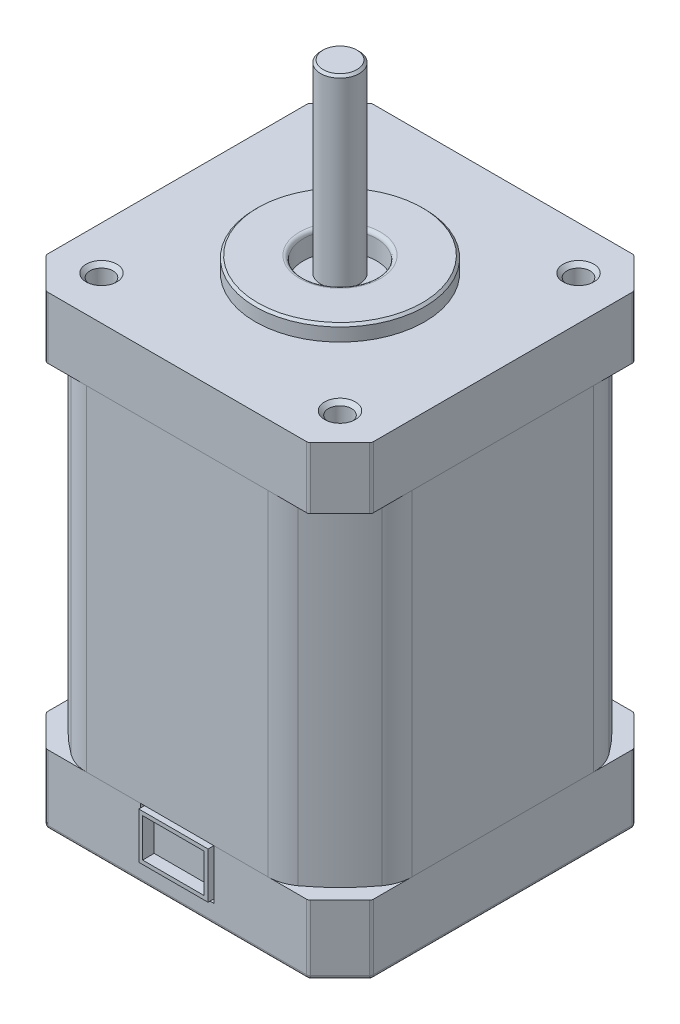
SolidWorks part; units mm, degrees
ref_plane "Спереди" through (0, 0, 0) normal (0, 0, 1) x (1, 0, 0)
ref_plane "Сверху" through (0, 0, 0) normal (0, 1, 0) x (1, 0, 0)
ref_plane "Справа" through (0, 0, 0) normal (1, 0, 0) x (0, 0, -1)
sketch "Эскиз1" plane through (0, 0, 0) normal (0, 1, 0) x (1, 0, 0)
  line L0 (-21.15, 17.0338) -> (-17.0338, 21.15)
  line L1 (-21.15, 21.15) -> (21.15, 21.15)
  line L2 (-21.15, 21.15) -> (-21.15, -21.15)
  line L3 (-21.15, -21.15) -> (21.15, -21.15)
  line L4 (21.15, 21.15) -> (21.15, -21.15)
  line L5 (-21.15, 21.15) -> (21.15, -21.15) construction
  line L6 (-21.15, -21.15) -> (21.15, 21.15) construction
  line L7 (-17.0338, 21.15) -> (17.0338, 21.15)
  line L8 (17.0338, 21.15) -> (21.15, 17.0338)
  line L9 (21.15, 17.0338) -> (21.15, -17.0338)
  line L10 (21.15, -17.0338) -> (17.0338, -21.15)
  line L11 (17.0338, -21.15) -> (-17.0338, -21.15)
  line L12 (-17.0338, -21.15) -> (-21.15, -17.0338)
  point P0 (0, 0)
  dimension "D1" = 42.3
  dimension "D2" = 54
extrude "Бобышка-Вытянуть1" add sketch "Эскиз1" along normal blind 9 contours L12 L3 L10 L4 L8 L1 L0 L2 region at (0, 0, 0)
extrude "Бобышка-Вытянуть2" add sketch "Эскиз1<3>" against normal blind 8 from offset 60.5 separate body contours L12 L3 L10 L4 L8 L1 L0 L2 region at (0, 0, 0)
sketch "Эскиз1<3>" plane through (0, 0, 0) normal (0, 1, 0) x (1, 0, 0) same geometry as "Эскиз1"
sketch "Эскиз2" plane through (0, 9, 0) normal (0, 1, 0) x (1, 0, 0)
  line L16 (-21.15, -17.0338) -> (-17.0338, -21.15)
  line L17 (-17.0338, -21.15) -> (17.0338, -21.15)
  line L18 (17.0338, -21.15) -> (21.15, -17.0338)
  line L19 (21.15, -17.0338) -> (21.15, 17.0338)
  line L20 (21.15, 17.0338) -> (17.0338, 21.15)
  line L21 (17.0338, 21.15) -> (-17.0338, 21.15)
  line L22 (-17.0338, 21.15) -> (-21.15, 17.0338)
  line L23 (-21.15, 17.0338) -> (-21.15, -17.0338)
  line L25 (-11.7974, -21.15) -> (11.7974, -21.15)
  line L27 (21.15, -11.7974) -> (21.15, 11.7974)
  line L29 (11.7974, 21.15) -> (-11.7974, 21.15)
  line L31 (-21.15, 11.7974) -> (-21.15, -11.7974)
  arc A0 (-20.1875, -14.7467) -> (-14.7467, -20.1875) centre (0, 0) ccw
  arc A1 (-14.7467, 20.1875) -> (-20.1875, 14.7467) centre (0, 0) ccw
  arc A2 (20.1875, 14.7467) -> (14.7467, 20.1875) centre (0, 0) ccw
  arc A3 (14.7467, -20.1875) -> (20.1875, -14.7467) centre (0, 0) ccw
  arc A4 (14.7467, 20.1875) -> (11.7974, 21.15) centre (11.7974, 16.15) ccw
  arc A5 (21.15, 11.7974) -> (20.1875, 14.7467) centre (16.15, 11.7974) ccw
  arc A6 (20.1875, -14.7467) -> (21.15, -11.7974) centre (16.15, -11.7974) ccw
  arc A7 (11.7974, -21.15) -> (14.7467, -20.1875) centre (11.7974, -16.15) ccw
  arc A8 (-14.7467, -20.1875) -> (-11.7974, -21.15) centre (-11.7974, -16.15) ccw
  arc A9 (-20.1875, -14.7467) -> (-21.15, -11.7974) centre (-16.15, -11.7974) cw
  arc A10 (-20.1875, 14.7467) -> (-21.15, 11.7974) centre (-16.15, 11.7974) ccw
  arc A11 (-11.7974, 21.15) -> (-14.7467, 20.1875) centre (-11.7974, 16.15) ccw
  point P22 (21.15, 13.3296)
  point P27 (13.3296, -21.15)
  point P36 (-13.3296, 21.15)
  dimension "D1" = 50
  dimension "D3" = 5
  dimension "D2" = 0
extrude "Бобышка-Вытянуть3" add sketch "Эскиз2" along normal blind 43.5 separate body
sketch "Эскиз3" plane through (0, 0, 0) normal (0, -1, 0) x (1, 0, 0)
  circle A0 centre (0, 0) radius 4.75
  dimension "D1" = 9.5
extrude "Вырез-Вытянуть1" cut sketch "Эскиз3" against normal blind 3
sketch "Эскиз4" plane through (0, 3, 0) normal (0, -1, 0) x (1, 0, 0)
  circle A0 centre (0, 0) radius 2.5
  circle A1 centre (0, 0) radius 4.75
  dimension "D1" = 5
extrude "Вырез-Вытянуть2" cut sketch "Эскиз4" against normal blind 0.5
sketch "Эскиз5" plane through (0, 3, 0) normal (0, -1, 0) x (1, 0, 0)
  circle A0 centre (0, 0) radius 0.5
  dimension "D1" = 1
extrude "Вырез-Вытянуть3" cut sketch "Эскиз5" against normal blind 0.5
chamfer "Фаска1" distance 0.3 angle 45 1 edges at (0, 3, -2.5)
fillet "Скругление1" radius 0.5 17 edges at (0, 0, 21.15) (19.0919, 0, 19.0919) (21.15, 0, 0) (19.0919, 0, -19.0919) (0, 0, -21.15) (-19.0919, 0, -19.0919) (-21.15, 0, 0) (-19.0919, 0, 19.0919) (0, 0, -4.75) (21.15, 4.5, 17.0338) (17.0338, 4.5, 21.15) (-17.0338, 4.5, 21.15) (-21.15, 4.5, 17.0338) (-21.15, 4.5, -17.0338) (-17.0338, 4.5, -21.15) (17.0338, 4.5, -21.15) (21.15, 4.5, -17.0338)
fillet "Скругление2" radius 0.5 8 edges at (21.15, 56.5, 17.0338) (17.0338, 56.5, 21.15) (-17.0338, 56.5, 21.15) (-21.15, 56.5, 17.0338) (-21.15, 56.5, -17.0338) (-17.0338, 56.5, -21.15) (17.0338, 56.5, -21.15) (21.15, 56.5, -17.0338)
sketch "Эскиз6" plane through (0, 60.5, 0) normal (0, 1, 0) x (1, 0, 0)
  circle A0 centre (0, 0) radius 11
  circle A1 centre (0, 0) radius 4.75
  dimension "D1" = 22
  dimension "D2" = 9.5
extrude "Бобышка-Вытянуть4" add sketch "Эскиз6" along normal blind 2
sketch "Эскиз7" plane through (0, 60.5, 0) normal (0, 1, 0) x (1, 0, 0)
  circle A2 centre (0, 0) radius 4.75
  circle A3 centre (0, 0) radius 4.75
  dimension "D1" = 0
extrude "Вырез-Вытянуть4" cut sketch "Эскиз7" against normal blind 1
chamfer "Фаска2" distance 0.3 angle 45 1 edges at (0, 62.5, 11)
fillet "Скругление3" radius 0.5 1 edges at (0, 62.5, 4.75)
sketch "Эскиз8" plane through (0, 60.5, 0) normal (0, 1, 0) x (1, 0, 0)
  circle A0 centre (0, 0) radius 2.5
  dimension "D1" = 5
extrude "Бобышка-Вытянуть5" add sketch "Эскиз8" along normal blind 24
chamfer "Фаска4" distance 0.3 angle 45 1 edges at (0, 84.5, 2.5)
sketch "Эскиз10" plane through (0, 0, 21.15) normal (0, 0, 1) x (1, 0, 0)
  line L0 (0, 0) -> (0, 9) construction
  line L1 (-11.7974, 9) -> (11.7974, 9) construction
  line L2 (-16.8267, 9) -> (16.8267, 9) construction
  line L3 (-4.75, 2.5) -> (4.75, 2.5)
  line L4 (-4.75, 2.5) -> (-4.75, 9)
  line L5 (-4.75, 9) -> (4.75, 9)
  line L6 (4.75, 2.5) -> (4.75, 9)
  line L7 (-4.75, 2.5) -> (4.75, 9) construction
  line L8 (-4.75, 9) -> (4.75, 2.5) construction
  point P5 (0, 5.75)
  dimension "D1" = 9.5
  dimension "D2" = 6.5
extrude "Вырез-Вытянуть6" cut sketch "Эскиз10" against normal blind 1
sketch "Эскиз11" plane through (0, 0, 20.15) normal (0, 0, 1) x (1, 0, 0)
  line L8 (4.5, 2.75) -> (4.5, 8.75)
  line L9 (4.5, 8.75) -> (-4.5, 8.75)
  line L10 (-4.5, 8.75) -> (-4.5, 2.75)
  line L11 (-4.5, 2.75) -> (4.5, 2.75)
  line L12 (4.5, 2.75) -> (4.5, 8.75)
  line L13 (4.5, 8.75) -> (-4.5, 8.75)
  line L14 (-4.5, 8.75) -> (-4.5, 2.75)
  line L15 (-4.5, 2.75) -> (4.5, 2.75)
  line L20 (4, 3.25) -> (4, 8.25)
  line L21 (4, 8.25) -> (-4, 8.25)
  line L22 (-4, 8.25) -> (-4, 3.25)
  line L23 (-4, 3.25) -> (4, 3.25)
  line L24 (4, 3.25) -> (4, 8.25)
  line L25 (4, 8.25) -> (-4, 8.25)
  line L26 (-4, 8.25) -> (-4, 3.25)
  line L27 (-4, 3.25) -> (4, 3.25)
  dimension "D1" = 0.25
  dimension "D2" = 0.75
extrude "Бобышка-Вытянуть6" add sketch "Эскиз11" along normal blind 1.5 separate body
sketch "Эскиз16" plane through (0, 60.5, 0) normal (0, 1, 0) x (1, 0, 0)
  line L1 (-15.5, 15.5) -> (15.5, 15.5) construction
  line L2 (-15.5, 15.5) -> (-15.5, -15.5) construction
  line L3 (-15.5, -15.5) -> (15.5, -15.5) construction
  line L4 (15.5, 15.5) -> (15.5, -15.5) construction
  line L5 (-15.5, 15.5) -> (15.5, -15.5) construction
  line L6 (-15.5, -15.5) -> (15.5, 15.5) construction
  circle A0 centre (-15.5, 15.5) radius 1.5
  circle A1 centre (15.5, 15.5) radius 1.5
  circle A2 centre (15.5, -15.5) radius 1.5
  circle A3 centre (-15.5, -15.5) radius 1.5
  point P0 (0, 0)
  dimension "D1" = 3
  dimension "D2" = 31
extrude "Вырез-Вытянуть9" cut sketch "Эскиз16" against normal blind 7
chamfer "Фаска35" distance 0.5 angle 45 4 edges at (-15.5, 60.5, 17) (15.5, 60.5, 17) (15.5, 60.5, -14) (-15.5, 60.5, -14)
